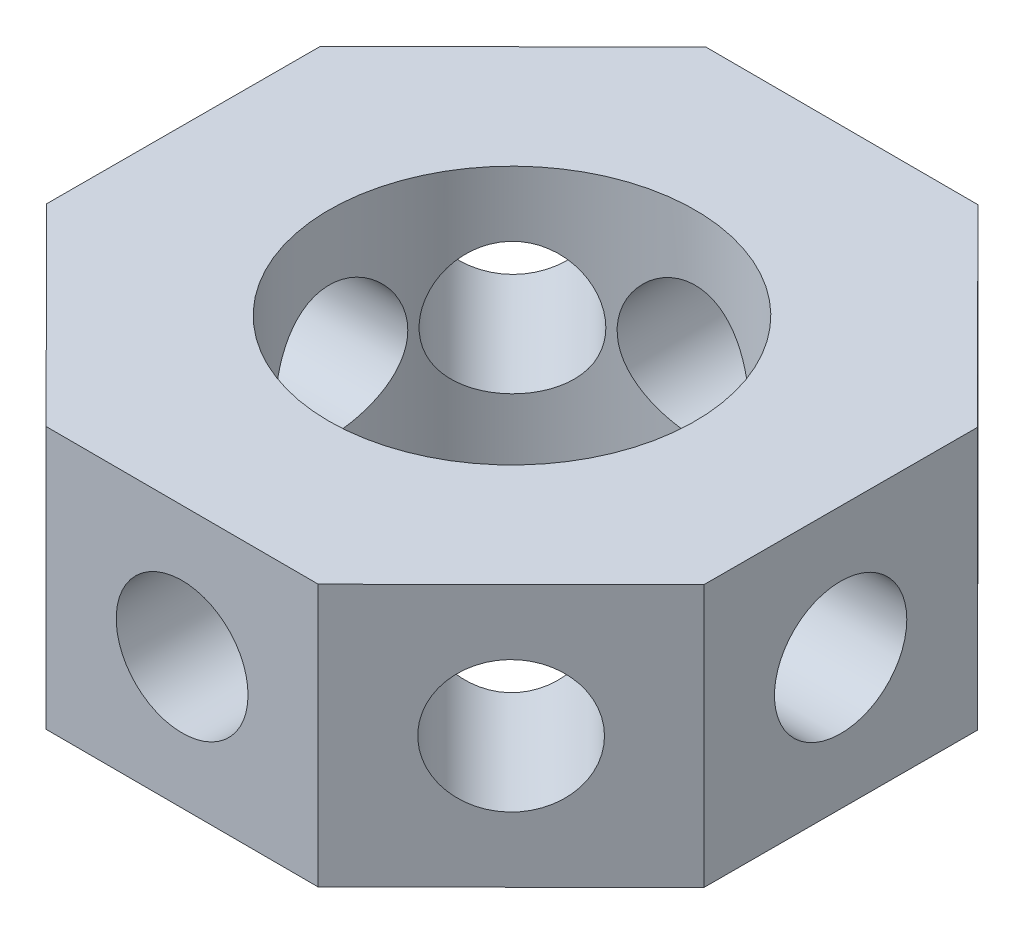
SolidWorks part; units mm, degrees
ref_plane "Front Plane" through (0, 0, 0) normal (0, 0, 1) x (1, 0, 0)
ref_plane "Top Plane" through (0, 0, 0) normal (0, 1, 0) x (1, 0, 0)
ref_plane "Right Plane" through (0, 0, 0) normal (1, 0, 0) x (0, 0, -1)
sketch "Sketch1" plane through (0, 0, 0) normal (0, 1, 0) x (1, 0, 0)
  line L1 (88.5763, -36.8862) -> (88.7154, 36.5504)
  line L2 (88.7154, 36.5504) -> (36.8862, 88.5763)
  line L3 (36.8862, 88.5763) -> (-36.5504, 88.7154)
  line L4 (-36.5504, 88.7154) -> (-88.5763, 36.8862)
  line L5 (-88.5763, 36.8862) -> (-88.7154, -36.5504)
  line L6 (-88.7154, -36.5504) -> (-36.8862, -88.5763)
  line L7 (-36.8862, -88.5763) -> (36.5504, -88.7154)
  line L8 (36.5504, -88.7154) -> (88.5763, -36.8862)
  circle A0 centre (0, 0) radius 88.646 construction
extrude "Boss-Extrude1" add sketch "Sketch1" along normal blind 35.306 and the other way blind 35.306
sketch "Sketch2" plane through (-0.1679, 0, 88.6458) normal (-0.0019, 0, 1) x (1, 0, 0.0019)
  line L0 (-36.7184, 0) -> (36.7184, 0) construction
  line L1 (-36.7184, 35.306) -> (-36.7184, -35.306) construction
  line L2 (36.7184, 35.306) -> (36.7184, -35.306) construction
  line L3 (0, 35.306) -> (0, 0) construction
  line L4 (-36.7184, 35.306) -> (36.7184, 35.306) construction
  circle A0 centre (0, 0) radius 17.78
  point P13 (0, 0)
  point P14 (0, 35.306)
extrude "Cut-Extrude1" cut sketch "Sketch2" against normal through all contours A0
pattern_circular "CirPattern1" count 4 every 45 about axis through (0, 35.306, 0) along (0, 1, 0) of "Cut-Extrude1"
sketch "Sketch3" plane through (0, 35.306, 0) normal (0, 1, 0) x (1, 0, 0)
  line L0 (-62.5633, 62.8008) -> (62.5633, -62.8008) construction
  line L1 (-36.5504, 88.7154) -> (-88.5763, 36.8862) construction
  line L2 (36.5504, -88.7154) -> (88.5763, -36.8862) construction
  line L3 (-62.8008, -62.5633) -> (62.8008, 62.5633) construction
  line L4 (-88.7154, -36.5504) -> (-36.8862, -88.5763) construction
  line L5 (88.7154, 36.5504) -> (36.8862, 88.5763) construction
  circle A0 centre (0, 0) radius 49.276
extrude "Cut-Extrude2" cut sketch "Sketch3" against normal through all
